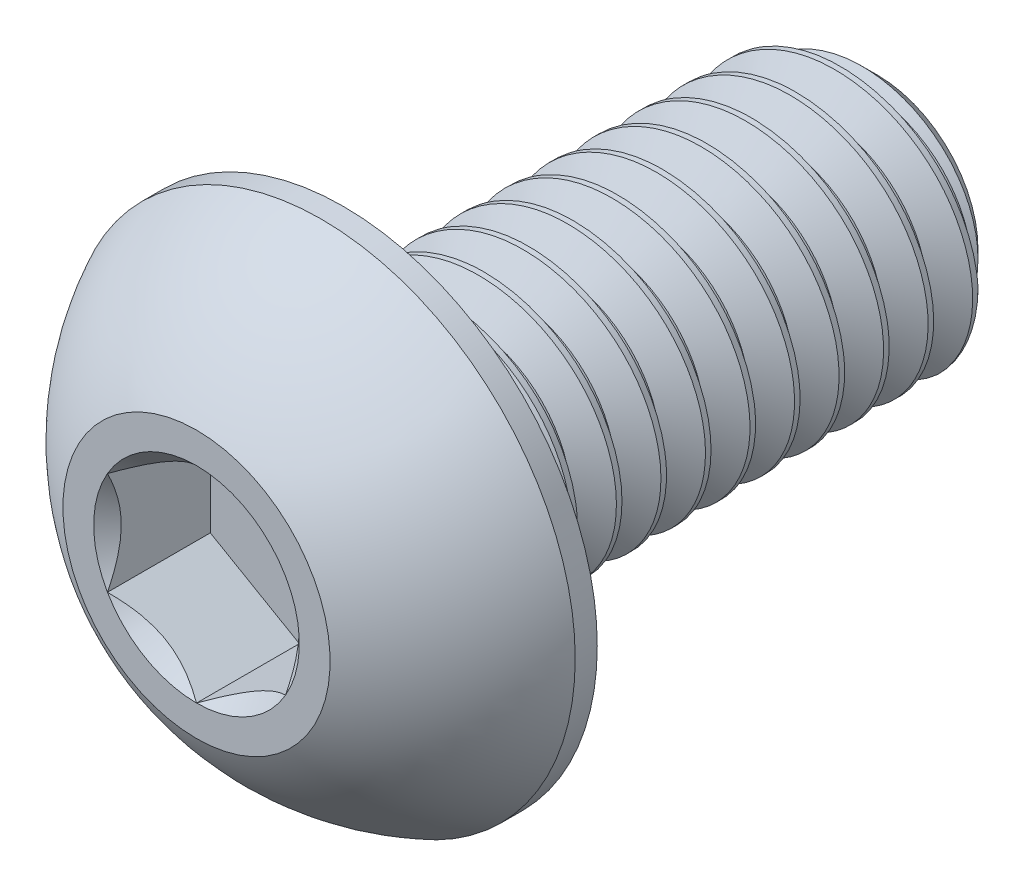
SolidWorks part; units mm, degrees
ref_plane "Front" through (0, 0, 0) normal (0, 0, 1) x (1, 0, 0)
ref_plane "Top" through (0, 0, 0) normal (0, 1, 0) x (1, 0, 0)
ref_plane "Right" through (0, 0, 0) normal (1, 0, 0) x (0, 0, -1)
sketch "Sketch1" plane through (0, 0, 0) normal (1, 0, 0) x (0, 0, -1)
  line L2 (1.65, 1.5) -> (7.65, 1.5)
  line L3 (7.65, 1.5) -> (7.65, 0)
  line L4 (7.65, 0) -> (1.65, 0)
  line L6 (1.4025, 2.85) -> (1.65, 2.85) construction
  line L7 (7.65, 1.5) -> (7.65, -1.5) construction
  line L8 (0, 0) -> (1.65, 0) construction
  line L9 (1.65, 2.85) -> (1.65, -2.85) construction
  line L11 (1.65, 1.5) -> (1.65, 0)
  line L13 (0, 1) -> (0, -1) construction
  line L14 (0, 1) -> (0, 1.5) construction
  arc A3 (0, 1.5) -> (1.4025, 2.85) centre (2.7948, 0) cw construction
  dimension "D1" = 0.2475
  dimension "Head Ht" = 1.65
  dimension "Head Dia" = 5.7
  dimension "Dia" = 3
  dimension "Lg" = 6
  dimension "Hex" = 2
revolve "Revolve1" add sketch "Sketch1" angle 360 mid plane about L4
sketch "Sketch3" plane through (0, 0, -7.65) normal (0, 0, -1) x (-1, 0, 0)
  circle A0 centre (0, 0) radius 1.5
curve "Helix/Spiral1" pitch 0.5 height 6.5 radius 1.5 centre (0, 0, -7.65) axis (0, 0, 1) start towards (0, 1, 0)
sketch "Sketch2" plane through (0, 0, 0) normal (1, 0, 0) x (0, 0, -1)
  line L0 (7.65, 1.5) -> (8.0875, 1.5)
  line L1 (8.0875, 1.5) -> (7.9, 1.1752)
  line L2 (7.9, 1.1752) -> (7.8375, 1.1752)
  line L3 (7.8375, 1.1752) -> (7.65, 1.5)
  line L4 (7.7438, 1.3376) -> (7.9938, 1.3376) construction
  dimension "D1" = 60
  dimension "D2" = 0.0625
  dimension "D3" = 0.25
chamfer "Chamfer1" distance 0.375 angle 45 1 edges at (0, 1.5, -7.65)
sweep "Cut-Sweep1" cut profiles "Sketch2" path "Helix/Spiral1" align with end faces yes
sketch "Sketch7" plane through (0, 0, 0) normal (1, 0, 0) x (0, 0, -1)
  line L6 (1.4025, 2.85) -> (1.65, 2.85) construction
  line L8 (0, 0) -> (1.65, 0) construction
  line L11 (1.65, 2.85) -> (1.65, -2.85) construction
  line L12 (1.4025, 2.85) -> (1.65, 2.85)
  line L13 (0, 0) -> (1.65, 0)
  line L14 (0, 1) -> (0, -1) construction
  line L15 (1.65, 2.85) -> (1.65, 0)
  line L16 (0, 1.5) -> (0, 0)
  arc A2 (1.4025, 2.85) -> (0, 1.5) centre (2.7948, 0) ccw construction
  arc A3 (1.4025, 2.85) -> (0, 1.5) centre (2.7948, 0) ccw
revolve "Revolve2" add sketch "Sketch7" angle 360 mid plane about L13
sketch "Sketch5" plane through (0, 0, 0) normal (0, 0, 1) x (1, 0, 0)
  line L1 (1, -0.5774) -> (1, 0.5774)
  line L2 (1, 0.5774) -> (0, 1.1547)
  line L3 (0, 1.1547) -> (-1, 0.5774)
  line L4 (-1, 0.5774) -> (-1, -0.5774)
  line L5 (-1, -0.5774) -> (0, -1.1547)
  line L6 (0, -1.1547) -> (1, -0.5774)
  circle A0 centre (0, 0) radius 1 construction
extrude "Cut-Extrude2" cut sketch "Sketch5" against normal blind 1.155
sketch "Sketch6" plane through (0, 0, 0) normal (0, 0, 1) x (1, 0, 0)
  circle A0 centre (0, 0) radius 1.1547
extrude "Cut-Extrude3" cut sketch "Sketch6" against normal blind 1.155 draft 45
sketch "Sketch9" [suppressed] plane through (0, 0, -6.6) normal (0, 0, 1) x (1, 0, 0)
  circle A2 centre (0, 0) radius 6
extrude "Boss-Extrude2" [suppressed] add sketch "Sketch9" against normal offset from surface (19 mm away) 32 up to face at (0, 1.125, -7.65)
sketch "Sketch10" plane through (0, 0, 0) normal (1, 0, 0) x (0, 0, -1)
  line L0 (7.65, 1.5) -> (7.65, -1.5) construction
  point P0 (6.9, -1.5)
  dimension "D1" = 0.75
equation "\"D3@Helix/Spiral1\" = \"Lg@Sketch1\" + \"D4@Helix/Spiral1\""
equation "\"D2@Sketch2\" = \"D4@Helix/Spiral1\" * .125"
equation "\"D3@Sketch2\" = \"D4@Helix/Spiral1\" * .5"
equation "\"D1@Chamfer1\" = \"D4@Helix/Spiral1\" * .75"
equation "\"D1@Cut-Extrude2\" = \"Head Ht@Sketch1\" * .7"
equation "\"D1@Sketch1\" = \"Head Ht@Sketch1\" * .15"
equation "\"D1@Sketch10\" = \"D4@Helix/Spiral1\" * 1.5"
equation "\"D1@Cut-Extrude3\" = \"D1@Cut-Extrude2\""
